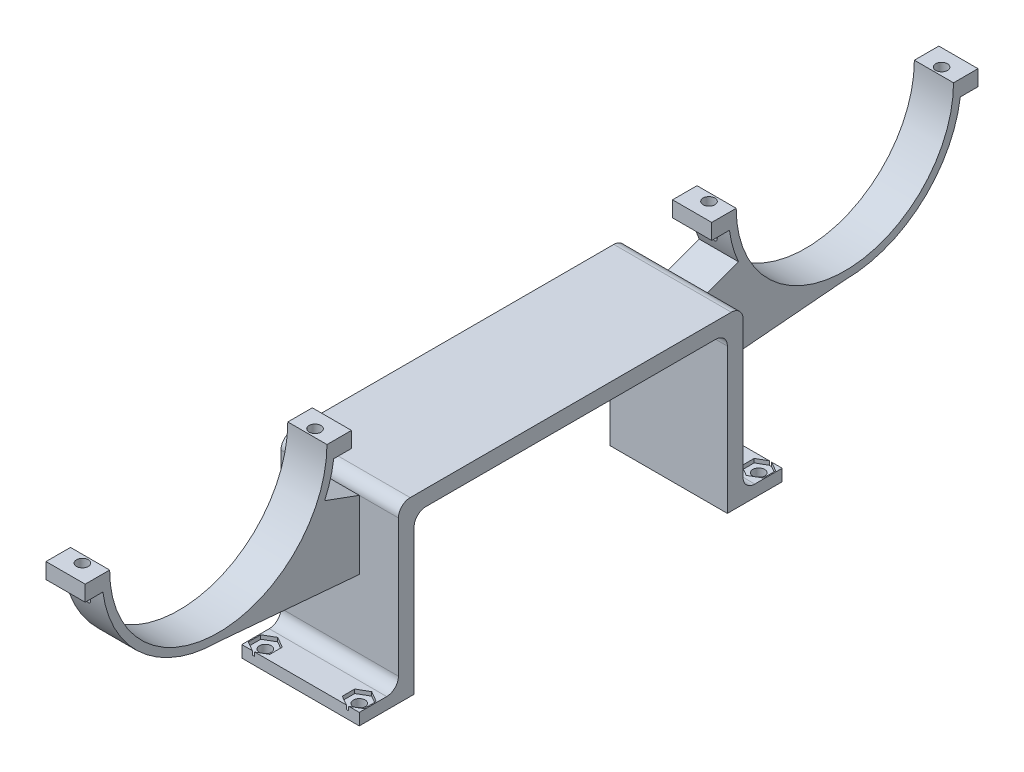
SolidWorks part; units mm, degrees
ref_plane "前视基准面" through (0, 0, 0) normal (0, 0, 1) x (1, 0, 0)
ref_plane "上视基准面" through (0, 0, 0) normal (0, 1, 0) x (1, 0, 0)
ref_plane "右视基准面" through (0, 0, 0) normal (1, 0, 0) x (0, 0, -1)
sketch "草图1" plane through (0, 0, 0) normal (1, 0, 0) x (0, 0, -1)
  line L0 (-40, -0.3448) -> (-40, 36.6552)
  line L1 (-37, 39.6552) -> (37, 39.6552)
  line L2 (0, 9.993) -> (0, 39.6552) construction
  line L3 (-44, 5.6552) -> (-44, 40.6552)
  line L4 (-41, 43.6552) -> (41, 43.6552)
  line L5 (0, 0) -> (0, 39.6552) construction
  line L6 (0, 39.6552) -> (0, 50.2262) construction
  line L7 (4, 0) -> (4, 43.6552) construction
  line L8 (-44, 43.6552) -> (4, 43.6552) construction
  line L9 (-40, -0.3448) -> (-54, -0.3448)
  line L10 (-54, -0.3448) -> (-54, 2.6552)
  line L11 (-54, 2.6552) -> (-47, 2.6552)
  line L12 (-44, -0.3448) -> (-44, 43.6552) construction
  line L13 (-40, -0.3448) -> (-40, 39.6552) construction
  line L14 (-40, 39.6552) -> (0, 39.6552) construction
  line L15 (54, 2.6552) -> (47, 2.6552)
  line L16 (54, -0.3448) -> (54, 2.6552)
  line L17 (40, -0.3448) -> (54, -0.3448)
  line L18 (44, 5.6552) -> (44, 40.6552)
  line L19 (40, -0.3448) -> (40, 36.6552)
  arc A0 (-40, 36.6552) -> (-37, 39.6552) centre (-37, 36.6552) cw
  arc A1 (-44, 40.6552) -> (-41, 43.6552) centre (-41, 40.6552) cw
  arc A2 (-47, 2.6552) -> (-44, 5.6552) centre (-47, 5.6552) ccw
  arc A3 (47, 2.6552) -> (44, 5.6552) centre (47, 5.6552) cw
  arc A4 (44, 40.6552) -> (41, 43.6552) centre (41, 40.6552) ccw
  arc A5 (40, 36.6552) -> (37, 39.6552) centre (37, 36.6552) ccw
  point P11 (40, 39.6552)
  point P18 (-40, 39.6552)
  point P36 (0, 43.6552)
  dimension "D6" = 3
  dimension "D1" = 40
  dimension "D2" = 40
  dimension "D3" = 4
  dimension "D4" = 3
  dimension "D5" = 10
extrude "凸台-拉伸1" add sketch "草图1" along normal blind 15 and the other way blind 15
sketch "草图2" plane through (15, 0, 0) normal (1, 0, 0) x (0, 0, -1)
  line L0 (-80, 56.0166) -> (0, 0) construction
  line L2 (-52.25, 56.0166) -> (-46, 56.0166)
  line L3 (-46, 56.0166) -> (-46, 52.0166)
  line L4 (-46, 52.0166) -> (-50.5201, 52.0166)
  line L5 (-114, 52.0166) -> (-109.4799, 52.0166)
  line L6 (-114, 56.0166) -> (-114, 52.0166)
  line L7 (-107.75, 56.0166) -> (-114, 56.0166)
  line L8 (-80, 83.7666) -> (-80, 130.2331) construction
  line L9 (-37, 39.6552) -> (37, 39.6552) construction
  line L10 (-80, 26.2666) -> (-44, 23.1552)
  line L11 (-44, 40.6552) -> (-44, 5.6552) construction
  line L12 (-52.8306, 43.8969) -> (-44, 40.6552)
  line L13 (-44, 40.6552) -> (-44, 23.1552)
  line L14 (0, 0) -> (0, -3.9568) construction
  line L15 (52.8306, 43.8969) -> (44, 40.6552)
  line L16 (46, 52.0166) -> (50.5201, 52.0166)
  line L17 (46, 56.0166) -> (46, 52.0166)
  line L18 (52.25, 56.0166) -> (46, 56.0166)
  line L19 (107.75, 56.0166) -> (114, 56.0166)
  line L20 (114, 56.0166) -> (114, 52.0166)
  line L21 (114, 52.0166) -> (109.4799, 52.0166)
  line L22 (80, 26.2666) -> (44, 23.1552)
  line L23 (44, 40.6552) -> (44, 23.1552)
  arc A0 (-107.75, 56.0166) -> (-52.25, 56.0166) centre (-80, 56.0166) ccw
  arc A1 (-109.4799, 52.0166) -> (-80, 26.2666) centre (-80, 56.0166) ccw
  arc A2 (-52.8306, 43.8969) -> (-50.5201, 52.0166) centre (-80, 56.0166) ccw
  arc A3 (52.8306, 43.8969) -> (50.5201, 52.0166) centre (80, 56.0166) cw
  arc A4 (109.4799, 52.0166) -> (80, 26.2666) centre (80, 56.0166) cw
  arc A5 (107.75, 56.0166) -> (52.25, 56.0166) centre (80, 56.0166) cw
  dimension "D2" = 55.5
  dimension "D5" = 2
  dimension "D1" = 80
  dimension "D3" = 4
  dimension "D4" = 145
  dimension "D6" = 34
extrude "凸台-拉伸2" add sketch "草图2" along normal blind 5 and the other way blind 5 from offset 15 offset against normal yes
sketch "草图3" plane through (0, 56.0166, 0) normal (0, 1, 0) x (1, 0, 0)
  line L0 (0, 114) -> (0, 46) construction
  line L1 (-5, 114) -> (5, 114) construction
  line L2 (-5, 46) -> (5, 46) construction
  line L3 (0, 80) -> (19.919, 80) construction
  line L4 (0, 0) -> (32.9208, 0) construction
  line L5 (0, -80) -> (19.919, -80) construction
  line L6 (0, -114) -> (0, -46) construction
  circle A0 centre (0, 109.7) radius 1.5
  circle A1 centre (0, 50.3) radius 1.5
  circle A2 centre (0, -50.3) radius 1.5
  circle A3 centre (0, -109.7) radius 1.5
  dimension "D1" = 3
  dimension "D2" = 29.7
extrude "切除-拉伸1" cut sketch "草图3" against normal blind 11
sketch "草图4" plane through (0, 2.6552, 0) normal (0, 1, 0) x (1, 0, 0)
  line L0 (-15, -54) -> (15, -54) construction
  line L1 (-15, -47) -> (-15, -54) construction
  line L2 (15, -47) -> (15, -54) construction
  line L3 (0, 0) -> (-52.2398, 0) construction
  circle A0 centre (-12, -51) radius 1.5
  circle A1 centre (12, -51) radius 1.5
  circle A2 centre (12, 51) radius 1.5
  circle A3 centre (-12, 51) radius 1.5
  dimension "D1" = 3
  dimension "D3" = 3
  dimension "D4" = 3
  dimension "D5" = 3
  dimension "D6" = 3
  dimension "D2" = 3
extrude "切除-拉伸2" cut sketch "草图4" against normal blind 11
sketch "草图5" plane through (0, 2.6552, 0) normal (0, 1, 0) x (1, 0, 0)
  line L0 (0, 0) -> (29.035, 0) construction
  line L1 (-12, 54.1754) -> (-14.75, 52.5877)
  line L2 (-14.75, 52.5877) -> (-14.75, 49.4123)
  line L3 (-14.75, 49.4123) -> (-12, 47.8246)
  line L4 (-12, 47.8246) -> (-9.25, 49.4123)
  line L5 (-9.25, 49.4123) -> (-9.25, 52.5877)
  line L6 (-9.25, 52.5877) -> (-12, 54.1754)
  line L7 (12, 54.1754) -> (9.25, 52.5877)
  line L8 (9.25, 52.5877) -> (9.25, 49.4123)
  line L9 (9.25, 49.4123) -> (12, 47.8246)
  line L10 (12, 47.8246) -> (14.75, 49.4123)
  line L11 (14.75, 49.4123) -> (14.75, 52.5877)
  line L12 (14.75, 52.5877) -> (12, 54.1754)
  line L13 (14.75, -52.5877) -> (12, -54.1754)
  line L14 (14.75, -49.4123) -> (14.75, -52.5877)
  line L15 (12, -47.8246) -> (14.75, -49.4123)
  line L16 (9.25, -49.4123) -> (12, -47.8246)
  line L17 (9.25, -52.5877) -> (9.25, -49.4123)
  line L18 (12, -54.1754) -> (9.25, -52.5877)
  line L19 (-9.25, -52.5877) -> (-12, -54.1754)
  line L20 (-9.25, -49.4123) -> (-9.25, -52.5877)
  line L21 (-12, -47.8246) -> (-9.25, -49.4123)
  line L22 (-14.75, -49.4123) -> (-12, -47.8246)
  line L23 (-14.75, -52.5877) -> (-14.75, -49.4123)
  line L24 (-12, -54.1754) -> (-14.75, -52.5877)
  circle A0 centre (-12, 51) radius 2.75 construction
  circle A1 centre (12, 51) radius 2.75 construction
  circle A2 centre (12, -51) radius 2.75 construction
  circle A3 centre (-12, -51) radius 2.75 construction
  dimension "D1" = 5.5
  dimension "D2" = 5.5
extrude "切除-拉伸3" cut sketch "草图5" against normal blind 1
